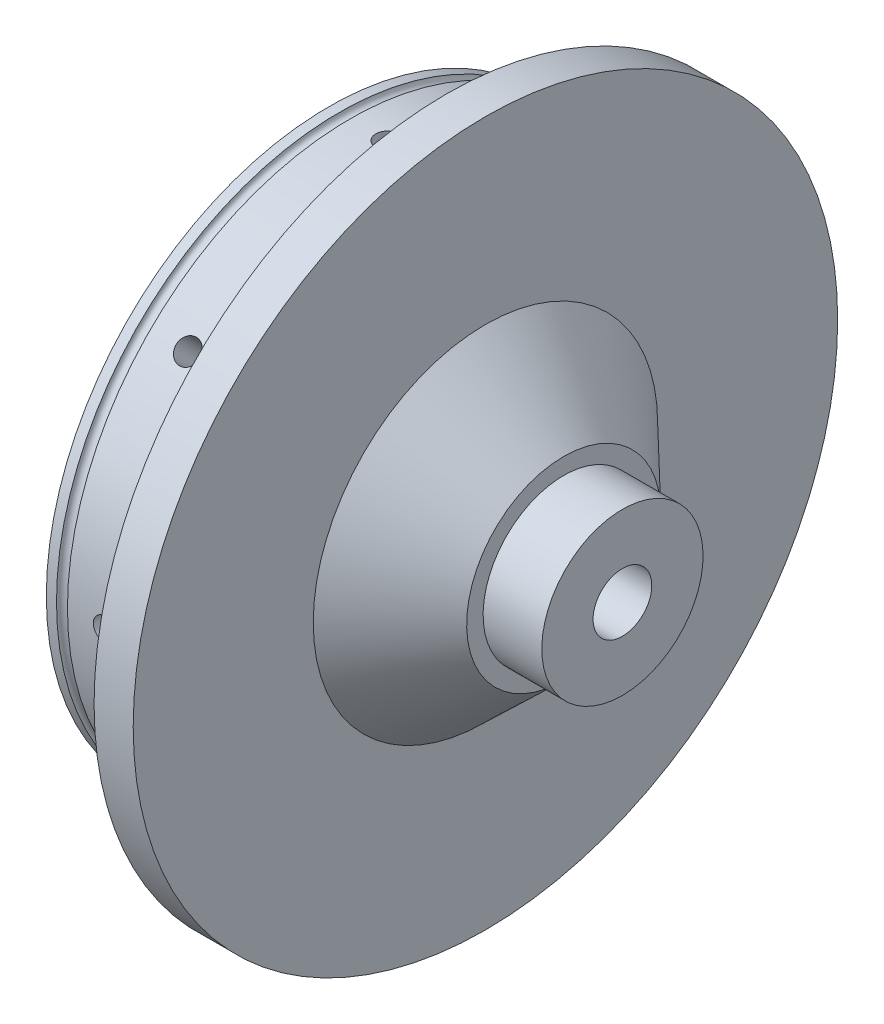
SolidWorks part; units mm, degrees
material "7075-T6 (SN)"
ref_plane "Front Plane" through (0, 0, 0) normal (0, 0, 1) x (1, 0, 0)
ref_plane "Top Plane" through (0, 0, 0) normal (0, 1, 0) x (1, 0, 0)
ref_plane "Right Plane" through (0, 0, 0) normal (1, 0, 0) x (0, 0, -1)
sketch "Sketch1" plane through (0, 0, 0) normal (1, 0, 0) x (0, 0, -1)
  circle A0 centre (0, 0) radius 57.15
  dimension "D1" = 114.3
extrude "Boss-Extrude1" add sketch "Sketch1" along normal blind 6.35
sketch "Sketch2" plane through (0, 0, 0) normal (-1, 0, 0) x (0, 0, 1)
  circle A0 centre (0, 0) radius 45.847
  dimension "D1" = 91.694
extrude "Boss-Extrude2" add sketch "Sketch2" along normal blind 19.05
sketch "Sketch3" plane through (-19.05, 0, 0) normal (-1, 0, 0) x (0, 0, 1)
  circle A0 centre (0, 0) radius 38.227
  dimension "D1" = 76.454
extrude "Cut-Extrude1" cut sketch "Sketch3" against normal blind 6.35
sketch "Sketch5" plane through (0, 0, 0) normal (0, 0, 1) x (1, 0, 0)
  line L0 (0, 45.847) -> (-19.05, 45.847) construction
  line L1 (-19.05, 45.847) -> (-19.05, -45.847) construction
  line L2 (0, 0) -> (-28.6633, 0) construction
  circle A0 centre (-16.51, 45.847) radius 0.889
  dimension "D1" = 1.778
  dimension "D2" = 2.54
revolve "Cut-Revolve1" cut sketch "Sketch5" angle 360 about L2
ref_plane "Plane1" through (0, 0, 45.847) normal (0, 0, 1) x (1, 0, 0)
sketch "Sketch6" plane through (0, 0, 45.847) normal (0, 0, 1) x (1, 0, 0)
  line L0 (0, 45.847) -> (0, -45.847) construction
  circle A0 centre (-9.525, 0) radius 1.905
  dimension "D1" = 3.81
  dimension "D2" = 9.525
extrude "Cut-Extrude3" cut sketch "Sketch6" against normal blind 6.35
pattern_circular "CirPattern1" count 8 every 45 about axis through (-19.05, 0, 0) along (1, 0, 0) of "Cut-Extrude3"
sketch "Sketch10" plane through (-12.7, 0, 0) normal (-1, 0, 0) x (0, 0, 1)
  circle A0 centre (0, 33.3375) radius 1.1303
  circle A1 centre (23.5732, 23.5732) radius 1.1303
  circle A2 centre (33.3375, 0) radius 1.1303
  circle A3 centre (23.5732, -23.5732) radius 1.1303
  circle A4 centre (0, -33.3375) radius 1.1303
  circle A5 centre (-23.5732, -23.5732) radius 1.1303
  circle A6 centre (-33.3375, 0) radius 1.1303
  circle A7 centre (-23.5732, 23.5732) radius 1.1303
  point P19 (0, 0)
  dimension "D2" = 2.2606
  dimension "D1" = 33.3375
  dimension "D3" = 8
extrude "Cut-Extrude5" cut sketch "Sketch10" against normal blind 5.08
sketch "Sketch17" plane through (0, 0, 0) normal (0, 0, 1) x (1, 0, 0)
  line L1 (6.35, -57.15) -> (6.35, 57.15) construction
  line L2 (19.05, 0) -> (6.35, 0)
  line L4 (19.05, 0) -> (19.05, 15.748)
  line L7 (19.05, 15.748) -> (6.35, 27.94)
  line L9 (6.35, 27.94) -> (6.35, 0)
  dimension "D1" = 27.94
  dimension "D2" = 15.748
  dimension "D3" = 12.7
revolve "Revolve1" add sketch "Sketch17" angle 360 about L2
sketch "Sketch18" plane through (19.05, 0, 0) normal (1, 0, 0) x (0, 0, -1)
  circle A0 centre (0, 0) radius 13.081
  dimension "D1" = 26.162
extrude "Boss-Extrude6" add sketch "Sketch18" along normal blind 9.525
sketch "Sketch19" plane through (28.575, 0, 0) normal (1, 0, 0) x (0, 0, -1)
  circle A0 centre (0, 0) radius 4.7625
  dimension "D1" = 9.525
extrude "Cut-Extrude7" cut sketch "Sketch19" against normal through all
sketch "Sketch20" plane through (0, 0, 0) normal (0, 0, 1) x (1, 0, 0)
  line L0 (19.05, 4.7625) -> (-12.7, 4.7625)
  line L1 (-12.7, 38.227) -> (-12.7, -38.227) construction
  line L2 (-12.7, 4.7625) -> (-12.7, 30.1625)
  line L3 (-12.7, 30.1625) -> (19.05, 4.7625)
  line L4 (0, 0) -> (-28.3532, 0) construction
  dimension "D1" = 4.7625
  dimension "D2" = 31.75
  dimension "D3" = 25.4
revolve "Cut-Revolve2" cut sketch "Sketch20" angle 360 about L4
